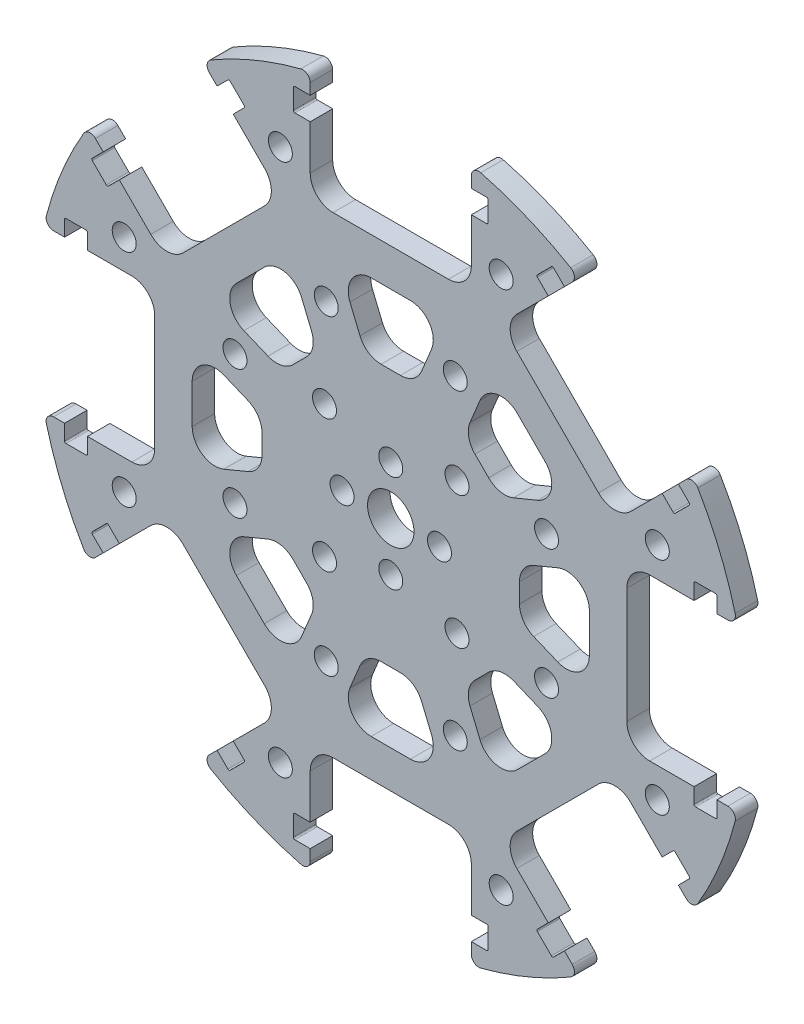
SolidWorks part; units mm, degrees
material "5052-H34"
ref_plane "正面" through (0, 0, 0) normal (0, 0, 1) x (1, 0, 0)
ref_plane "平面" through (0, 0, 0) normal (0, 1, 0) x (1, 0, 0)
ref_plane "右側面" through (0, 0, 0) normal (1, 0, 0) x (0, 0, -1)
sketch "ｽｹｯﾁ1" plane through (0, 0, 0) normal (0, 0, 1) x (1, 0, 0)
  circle A0 centre (0, 0) radius 47.5
  dimension "D1" = 95
extrude "ﾎﾞｽ - 押し出し1" add sketch "ｽｹｯﾁ1" along normal blind 3
sketch "ｽｹｯﾁ2" plane through (0, 0, 3) normal (0, 0, 1) x (1, 0, 0)
  line L0 (0, 0) -> (0, 47.5) construction
  line L1 (-10.75, 43.525) -> (-10.75, 52.5)
  line L2 (-10.75, 31.5) -> (10.75, 31.5)
  line L3 (-10.75, 31.5) -> (-10.75, 40.475)
  line L4 (-10.75, 52.5) -> (10.75, 52.5)
  line L5 (10.75, 31.5) -> (10.75, 40.475)
  line L6 (-10.75, 31.5) -> (10.75, 52.5) construction
  line L7 (-10.75, 52.5) -> (10.75, 31.5) construction
  line L8 (-13, 43.525) -> (-10.75, 43.525)
  line L9 (-13, 43.525) -> (-13, 40.475)
  line L10 (-13, 40.475) -> (-10.75, 40.475)
  line L11 (13, 43.525) -> (13, 40.475)
  line L12 (-13, 43.525) -> (13, 40.475) construction
  line L13 (-13, 40.475) -> (13, 43.525) construction
  line L14 (10.75, 43.525) -> (10.75, 52.5)
  line L15 (10.75, 43.525) -> (13, 43.525)
  line L17 (10.75, 40.475) -> (13, 40.475)
  circle A0 centre (0, 0) radius 47.5 construction
  point P5 (0, 42)
  point P10 (0, 42)
  dimension "D1" = 42
  dimension "D2" = 21.5
  dimension "D3" = 21
  dimension "D4" = 3.05
  dimension "D5" = 26
extrude "ｶｯﾄ - 押し出し1" cut sketch "ｽｹｯﾁ2" against normal through all
sketch "ｽｹｯﾁ3" plane through (0, 0, 3) normal (0, 0, 1) x (1, 0, 0)
  line L1 (-8.8388, -8.8388) -> (8.8388, -8.8388) construction
  line L2 (-8.8388, -8.8388) -> (-8.8388, 8.8388) construction
  line L3 (-8.8388, 8.8388) -> (8.8388, 8.8388) construction
  line L4 (8.8388, -8.8388) -> (8.8388, 8.8388) construction
  line L5 (-8.8388, -8.8388) -> (8.8388, 8.8388) construction
  line L6 (-8.8388, 8.8388) -> (8.8388, -8.8388) construction
  circle A0 centre (0, 0) radius 3.1
  circle A1 centre (0, 0) radius 6.5 construction
  circle A2 centre (0, 6.5) radius 1.6
  circle A3 centre (6.5, 0) radius 1.6
  circle A4 centre (0, -6.5) radius 1.6
  circle A5 centre (-6.5, 0) radius 1.6
  circle A6 centre (0, 0) radius 12.5 construction
  circle A7 centre (8.8388, 8.8388) radius 1.6
  circle A8 centre (8.8388, -8.8388) radius 1.6
  circle A9 centre (-8.8388, -8.8388) radius 1.6
  circle A10 centre (-8.8388, 8.8388) radius 1.6
  dimension "D1" = 6.2
  dimension "D2" = 13
  dimension "D3" = 3.2
  dimension "D5" = 25
  dimension "D6" = 3.2
  dimension "D4" = 4
  dimension "D7" = 4
extrude "ｶｯﾄ - 押し出し2" cut sketch "ｽｹｯﾁ3" against normal through all and the other way through all
sketch "ｽｹｯﾁ4" plane through (0, 0, 3) normal (0, 0, 1) x (1, 0, 0)
  line L0 (0, 31.5) -> (0, 0) construction
  line L1 (-10.75, 31.5) -> (10.75, 31.5) construction
  line L2 (0, 0) -> (14.7333, 35.5694) construction
  circle A0 centre (0, 0) radius 22.5 construction
  circle A1 centre (0, 0) radius 38.5 construction
  circle A2 centre (14.7333, 35.5694) radius 1.6
  circle A3 centre (8.6104, 20.7873) radius 1.6
  dimension "D1" = 45
  dimension "D2" = 77
  dimension "D4" = 3.2
  dimension "D3" = 22.5
extrude "ｶｯﾄ - 押し出し3" cut sketch "ｽｹｯﾁ4" against normal through all
sketch "ｽｹｯﾁ5" plane through (0, 0, 3) normal (0, 0, 1) x (1, 0, 0)
  line L0 (0, 0) -> (14.7333, 35.5694) construction
  line L1 (-10.75, 31.5) -> (10.75, 31.5) construction
  line L2 (-10.75, 31.5) -> (10.75, 31.5) construction
  line L3 (-7.1883, 26.5) -> (7.1883, 26.5)
  line L4 (-3.3281, 17.1806) -> (-7.1883, 26.5)
  line L5 (0, 31.5) -> (0, 0) construction
  line L6 (-10.75, 26.5) -> (10.75, 26.5) construction
  line L9 (-3.3281, 17.1806) -> (3.3281, 17.1806)
  line L10 (3.3281, 17.1806) -> (7.1883, 26.5)
  circle A0 centre (0, 0) radius 17.5 construction
  dimension "D3" = 35
  dimension "D2" = 7
  dimension "D1" = 5
extrude "ｶｯﾄ - 押し出し4" cut sketch "ｽｹｯﾁ5" against normal through all and the other way through all
fillet "ﾌｨﾚｯﾄ1" radius 1 2 edges at (10.75, 46.2676, 1.5) (-10.75, 46.2676, 1.5)
fillet "ﾌｨﾚｯﾄ2" radius 0.2 4 edges at (13, 43.525, 1.5) (13, 40.475, 1.5) (-13, 43.525, 1.5) (-13, 40.475, 1.5)
fillet "ﾌｨﾚｯﾄ3" radius 3.05 2 edges at (10.75, 31.5, 1.5) (-10.75, 31.5, 1.5)
fillet "ﾌｨﾚｯﾄ4" radius 3.05 4 edges at (7.1883, 26.5, 1.5) (3.3281, 17.1806, 1.5) (-3.3281, 17.1806, 1.5) (-7.1883, 26.5, 1.5)
ref_axis "軸1" through (0, 0, 0) along (0, 0, 1)
pattern_circular "円形ﾊﾟﾀｰﾝ1" count 8 over 360 about axis through (0, 0, 0) along (0, 0, 1) of "ｶｯﾄ - 押し出し1", "ﾌｨﾚｯﾄ1", "ｶｯﾄ - 押し出し4", "ｶｯﾄ - 押し出し3", "ﾌｨﾚｯﾄ2", "ﾌｨﾚｯﾄ3", "ﾌｨﾚｯﾄ4"
